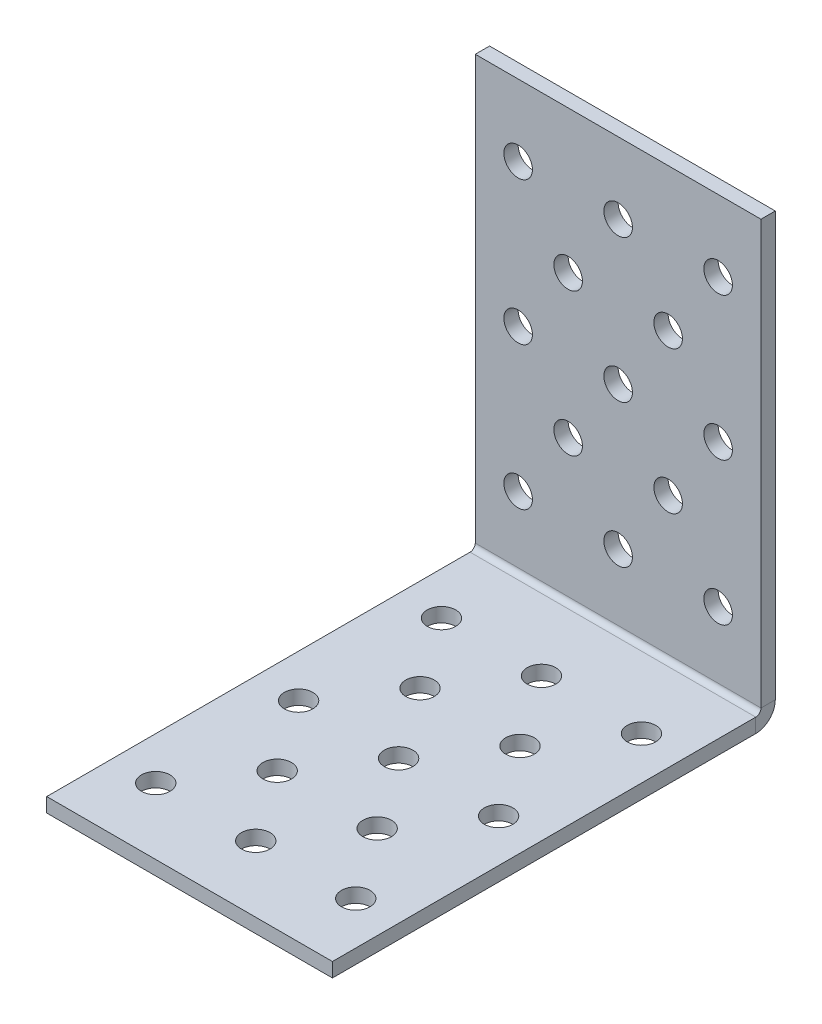
SolidWorks part; units mm, degrees
note: The reader was unsure of these and kept them because the rebuilt part matched: flange length of "Edge-Flange1".
ref_plane "Front Plane" through (0, 0, 0) normal (0, 0, 1) x (1, 0, 0)
ref_plane "Top Plane" through (0, 0, 0) normal (0, 1, 0) x (1, 0, 0)
ref_plane "Right Plane" through (0, 0, 0) normal (1, 0, 0) x (0, 0, -1)
sketch "Sketch1" plane through (0, 0, 0) normal (0, 0, 1) x (1, 0, 0)
  line L0 (-20, 50) -> (20, 50) construction
  line L1 (-20, 60) -> (20, 60)
  line L2 (-20, 60) -> (-20, 0)
  line L4 (20, 60) -> (20, 0)
  line L5 (-20, 60) -> (0, 0) construction
  line L6 (0, 0) -> (20, 60) construction
  line L7 (-20, 40) -> (20, 40) construction
  line L8 (0, 60) -> (0, 0) construction
  line L9 (-20, 30) -> (20, 30) construction
  line L10 (-20, 10) -> (20, 10) construction
  line L14 (-20, 0) -> (20, 0)
  line L16 (-20, -10) -> (20, -10) construction
  line L17 (-20, -30) -> (20, -30) construction
  line L18 (-20, -50) -> (20, -50) construction
  circle A0 centre (-14, 50) radius 2
  circle A1 centre (0, 50) radius 2
  circle A2 centre (14, 50) radius 2
  circle A3 centre (-7, 40) radius 2
  circle A4 centre (7, 40) radius 2
  circle A5 centre (-14, 30) radius 2
  circle A6 centre (-7, 20) radius 2
  circle A7 centre (7, 20) radius 2
  circle A8 centre (0, 30) radius 2
  circle A9 centre (14, 30) radius 2
  circle A10 centre (-14, 10) radius 2
  circle A13 centre (0, 10) radius 2
  circle A14 centre (14, 10) radius 2
  arc A30 (-9, -60) -> (-5, -60) centre (-7, -60) ccw [skipped]
  arc A31 (9, -60) -> (5, -60) centre (7, -60) ccw [skipped]
  circle A32 centre (7, 0) radius 2 [skipped]
  circle A33 centre (-7, 0) radius 2 [skipped]
  circle A34 centre (-14, -10) radius 2 [skipped]
  circle A35 centre (-7, -20) radius 2 [skipped]
  circle A36 centre (7, -20) radius 2 [skipped]
  circle A37 centre (0, -10) radius 2 [skipped]
  circle A38 centre (14, -10) radius 2 [skipped]
  circle A39 centre (-14, -30) radius 2 [skipped]
  circle A40 centre (-7, -40) radius 2 [skipped]
  circle A41 centre (7, -40) radius 2 [skipped]
  circle A42 centre (0, -30) radius 2 [skipped]
  circle A43 centre (14, -30) radius 2 [skipped]
  circle A44 centre (-14, -50) radius 2 [skipped]
  circle A45 centre (0, -50) radius 2 [skipped]
  circle A46 centre (14, -50) radius 2 [skipped]
  point P0 (0, 0)
  point P23 (0, 40)
  dimension "D5" = 14
  dimension "D6" = 14
  dimension "D7" = 7
  dimension "D8" = 7
  dimension "D9" = 4
  dimension "D13" = 10
  dimension "D2" = 40
  dimension "D3" = 10
  dimension "D4" = 10
  dimension "D11" = 10
  dimension "D12" = 60
  dimension "D10" = 6
base flange "Base-Flange1" sketch "Sketch1" thickness 2 reverse thickness direction no parameters "D1"=0.7366
edge flange "Edge-Flange1" sketch "Sketch6" flange angle 90 flange length 60 flange position material outside bend radius 0.7366 thickness 2 relief rectangular parameters "D6"=0
sketch "Sketch6" plane through (0, 0, 0) normal (0, -1, 0) x (1, 0, 0)
  line L0 (-20, 0) -> (20, 0) construction
  line L1 (-20, 0) -> (20, 0)
  line L2 (-20, 0) -> (-20, 60)
  line L3 (-20, 60) -> (20, 60)
  line L4 (20, 60) -> (20, 0)
  dimension "D1" = 60
bend "EdgeBend1" bend radius 0.7366 bend angle 90 parameters "D5"=1
sketch "Sketch7" plane through (0, 0, 0) normal (0, 1, 0) x (1, 0, 0)
  line L0 (0, 0) -> (0, -60) construction
  line L1 (20, -60) -> (-20, -60) construction
  line L3 (-20, -10.7366) -> (20, -10.7366) construction
  line L4 (-20, -60) -> (-20, -0.7366) construction
  line L5 (20, -0.7366) -> (20, -60) construction
  line L6 (-20, -20.7366) -> (20, -20.7366) construction
  line L8 (-20, -30.7366) -> (20, -30.7366) construction
  line L9 (-20, -50.7366) -> (20, -50.7366) construction
  line L10 (-20, -40.7366) -> (20, -40.7366) construction
  line L12 (-20, -0.7366) -> (20, -0.7366) construction
  circle A0 centre (-14, -10.7366) radius 2
  circle A1 centre (0, -10.7366) radius 2
  circle A2 centre (14, -10.7366) radius 2
  circle A3 centre (-7, -20.7366) radius 2
  circle A4 centre (7, -20.7366) radius 2
  circle A5 centre (-14, -30.7366) radius 2
  circle A8 centre (0, -30.7366) radius 2
  circle A9 centre (14, -30.7366) radius 2
  circle A13 centre (-7, -40.7366) radius 2
  circle A14 centre (7, -40.7366) radius 2
  circle A15 centre (14, -50.7366) radius 2
  circle A16 centre (0, -50.7366) radius 2
  circle A17 centre (-14, -50.7366) radius 2
  point P43 (0, 0)
  point P44 (0, 0)
  point P45 (0, 0)
  point P50 (0, 0)
  point P51 (0, 0)
  point P52 (0, 0)
  point P53 (0, 0)
  point P54 (0, 0)
  dimension "D1" = 14
  dimension "D2" = 14
  dimension "D5" = 14
  dimension "D6" = 14
  dimension "D7" = 4
  dimension "D9" = 7
  dimension "D10" = 10
  dimension "D4" = 10
  dimension "D11" = 4
  dimension "D12" = 4
  dimension "D3" = 10
  dimension "D8" = 7
extrude "Cut-Extrude1" cut sketch "Sketch7" against normal blind 10
sketch "Bend-Lines1" [suppressed] plane through (0, 0, 0) normal (0, 1, 0) x (1, 0, 0)
sketch "Bounding-Box1" [suppressed] plane through (0, 0, 0) normal (0, 1, 0) x (1, 0, 0)
sheet metal parameters "Sheet-Metal1" thickness 2 parameters "D1"=0.7366
flat pattern "Flat-Pattern1" [suppressed]
sketch "Bend-Lines2" plane through (0, 0, 0) normal (0, 1, 0) x (1, 0, 0)
sketch3d "Bounding-Box2" [suppressed]
  line L0 (20, 60, 0) -> (20, -60, 0) construction
  line L1 (-20, 60, 0) -> (-20, -60, 0) construction
  line L2 (20, 60, 0) -> (-20, 60, 0) construction
  line L3 (20, -60, 0) -> (-20, -60, 0) construction
sheet metal parameters "Sheet-Metal2" thickness 2 parameters "D1"=0.7366
flat pattern "Flat-Pattern1" [suppressed]
sketch "Bend-Lines2" plane through (0, 0, 0) normal (0, 1, 0) x (1, 0, 0)
sketch3d "Bounding-Box2" [suppressed]
  line L0 (20, 60, 0) -> (20, -60, 0) construction
  line L1 (-20, 60, 0) -> (-20, -60, 0) construction
  line L2 (20, 60, 0) -> (-20, 60, 0) construction
  line L3 (20, -60, 0) -> (-20, -60, 0) construction
bend of the flat pattern "Flatten-<EdgeBend1>1"
sheet metal parameters "Sheet-Metal3" thickness 2 parameters "D1"=0.7366
flat pattern "Flat-Pattern1"
sketch "Bend-Lines2" plane through (0, 0, 0) normal (0, 0, 1) x (1, 0, 0)
  line L0 (-20, -0.6273) -> (20, -0.6273) construction
  line L1 (-20, -0.6273) -> (20, -0.6273) construction
sketch3d "Bounding-Box2" [suppressed]
  line L0 (20, 60, 0) -> (20, -61.2546, 0) construction
  line L1 (-20, 60, 0) -> (-20, -61.2546, 0) construction
  line L2 (20, 60, 0) -> (-20, 60, 0) construction
  line L3 (20, -61.2546, 0) -> (-20, -61.2546, 0) construction
bend of the flat pattern "Flatten-<EdgeBend1>1"
